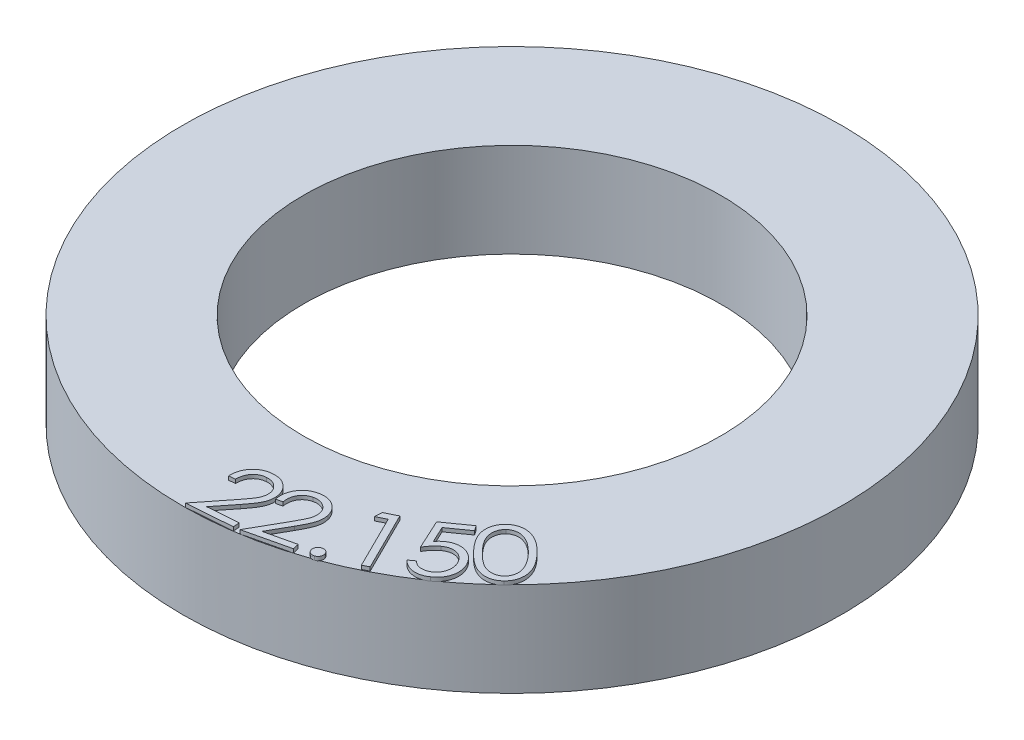
SolidWorks part; units mm, degrees
ref_plane "Front Plane" through (0, 0, 0) normal (0, 0, 1) x (1, 0, 0)
ref_plane "Top Plane" through (0, 0, 0) normal (0, 1, 0) x (1, 0, 0)
ref_plane "Right Plane" through (0, 0, 0) normal (1, 0, 0) x (0, 0, -1)
ref_axis "X" through (-88.99, 0, 0) along (1, 0, 0)
ref_axis "Y" through (0, 55, 0) along (0, -1, 0)
ref_axis "Z" through (0, 0, -88.99) along (0, 0, 1)
sketch "Sketch1" plane through (0, 0, 0) normal (0, 1, 0) x (1, 0, 0)
  circle A0 centre (0, 0) radius 17.5
  circle A1 centre (0, 0) radius 11.075
  dimension "D1" = 35
  dimension "D2" = 22.15
extrude "Boss-Extrude1" add sketch "Sketch1" along normal blind 5
sketch "Sketch8" plane through (0, 5, 0) normal (0, 1, 0) x (1, 0, 0)
  text T0 "22.150"
extrude "Boss-Extrude8" add sketch "Sketch8" along normal blind 0.2
